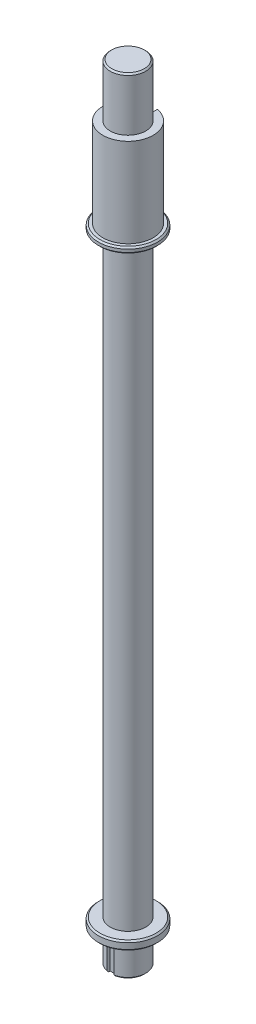
SolidWorks part; units mm, degrees
note: '?' marks a value the reader was unsure of.
ref_plane "Front Plane" through (0, 0, 0) normal (0, 0, 1) x (1, 0, 0)
ref_plane "Top Plane" through (0, 0, 0) normal (0, 1, 0) x (1, 0, 0)
ref_plane "Right Plane" through (0, 0, 0) normal (1, 0, 0) x (0, 0, -1)
sketch "Sketch2" plane through (0, 0, 0) normal (0, 0, 1) x (1, 0, 0)
  line L0 (0, 0) -> (6, 0)
  line L1 (6, 0) -> (6, 11)
  line L2 (6, 11) -> (10, 11)
  line L3 (10, 11) -> (10, 14)
  line L5 (0, 265) -> (0, 0)
  line L6 (10, 14) -> (6, 14)
  line L7 (6, 14) -> (6, 265)
  line L8 (6, 265) -> (0, 265)
  dimension "D1" = 11
  dimension "D2" = 6
  dimension "D3" = 3
  dimension "D4" = 10
  dimension "D5" = 265
revolve "Revolve1" add sketch "Sketch2" angle 360 about L5
sketch "Sketch3" plane through (0, 0, 0) normal (0, -1, 0) x (1, 0, 0)
  line L1 (-1.125, 7.125) -> (1.125, 7.125)
  line L2 (-1.125, 7.125) -> (-1.125, 4.875)
  line L3 (-1.125, 4.875) -> (1.125, 4.875)
  line L4 (1.125, 7.125) -> (1.125, 4.875)
  line L5 (-1.125, 7.125) -> (1.125, 4.875) construction
  line L6 (-1.125, 4.875) -> (1.125, 7.125) construction
  circle A0 centre (0, 0) radius 6 construction
  circle A1 centre (0, 0) radius 6 construction
  point P0 (0, 6)
  dimension "D1" = 2.25
extrude "Cut-Extrude1" cut sketch "Sketch3" against normal up to surface (11 mm away) up to face at (-10, 11, 0)
ref_axis "Axis1" through (0, 14, 0) along (0, 1, 0)?
chamfer "Chamfer1" distance 0.5 angle 45 4 edges at (-10, 11, 0) (-10, 14, 0) (-6, 265, 0) (0, 0, -6)
sketch "Sketch4" plane through (0, 265, 0) normal (0, 1, 0) x (1, 0, 0)
  circle A0 centre (0, 0) radius 8.5
  circle A1 centre (0, 0) radius 6 construction
  circle A2 centre (0, 0) radius 6
  dimension "D1" = 17
extrude "Boss-Extrude1" add sketch "Sketch4" against normal blind 48
sketch "Sketch5" plane through (0, 265, 0) normal (0, 1, 0) x (1, 0, 0)
  circle A0 centre (0, 0) radius 6 construction
  circle A1 centre (0, 0) radius 6
extrude "Cut-Extrude2" cut sketch "Sketch5" against normal blind 18 flip side to cut
sketch "Sketch6" plane through (0, 247, 0) normal (0, 1, 0) x (1, 0, 0)
  line L1 (-1.625, 10.125) -> (1.625, 10.125)
  line L2 (-1.625, 10.125) -> (-1.625, 6.875)
  line L3 (-1.625, 6.875) -> (1.625, 6.875)
  line L4 (1.625, 10.125) -> (1.625, 6.875)
  line L5 (-1.625, 10.125) -> (1.625, 6.875) construction
  line L6 (-1.625, 6.875) -> (1.625, 10.125) construction
  circle A0 centre (0, 0) radius 8.5 construction
  point P0 (0, 8.5)
  point P7 (0, 0)
  dimension "D1" = 3.25
extrude "Cut-Extrude3" cut sketch "Sketch6" against normal up to surface (30 mm away) up to face at (-6, 217, 0)
sketch "Sketch7" plane through (0, 217, 0) normal (0, -1, 0) x (1, 0, 0)
  circle A0 centre (0, 0) radius 6 construction
  circle A1 centre (0, 0) radius 6
  circle A2 centre (0, 0) radius 10
  dimension "D1" = 20
extrude "Boss-Extrude2" add sketch "Sketch7" along normal blind 2
chamfer "Chamfer2" distance 0.5 angle 45 3 edges at (10, 217, 0) (6, 215, 0) (10, 215, 0)
